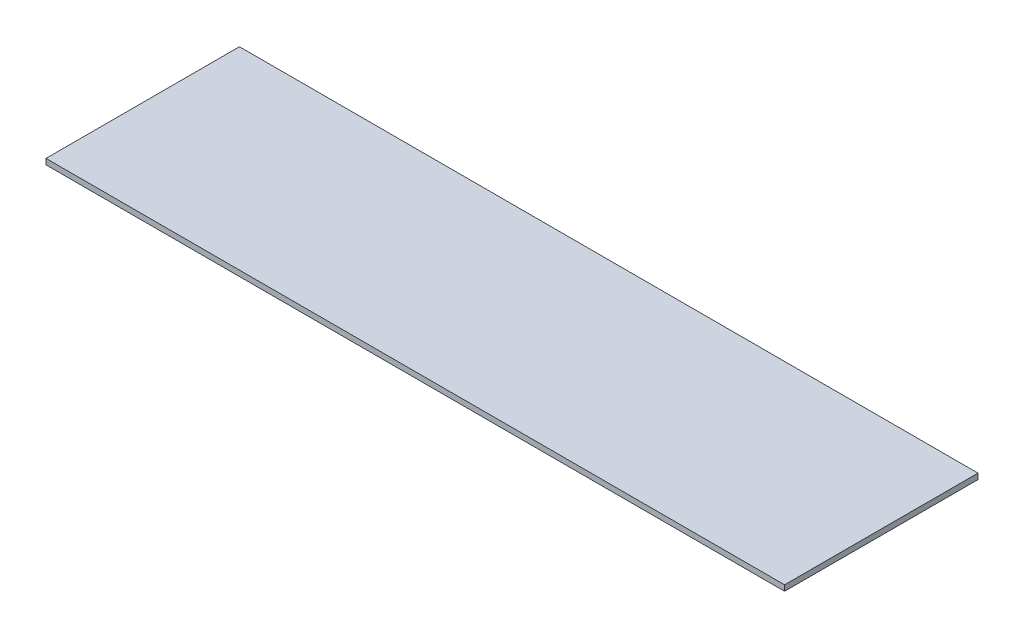
SolidWorks part; units mm, degrees
ref_plane "Ebene vorne" through (0, 0, 0) normal (0, 0, 1) x (1, 0, 0)
ref_plane "Ebene oben" through (0, 0, 0) normal (0, 1, 0) x (1, 0, 0)
ref_plane "Ebene rechts" through (0, 0, 0) normal (1, 0, 0) x (0, 0, -1)
sketch "Skizze1" plane through (0, 0, 0) normal (0, 1, 0) x (1, 0, 0)
  line L1 (-1050, -275) -> (1050, -275)
  line L2 (-1050, -275) -> (-1050, 275)
  line L3 (-1050, 275) -> (1050, 275)
  line L4 (1050, -275) -> (1050, 275)
  line L5 (-1050, -275) -> (1050, 275) construction
  line L6 (-1050, 275) -> (1050, -275) construction
  point P0 (0, 0)
  dimension "D1" = 550
  dimension "D2" = 2100
extrude "Aufsatz-Linear austragen1" add sketch "Skizze1" along normal blind 16
